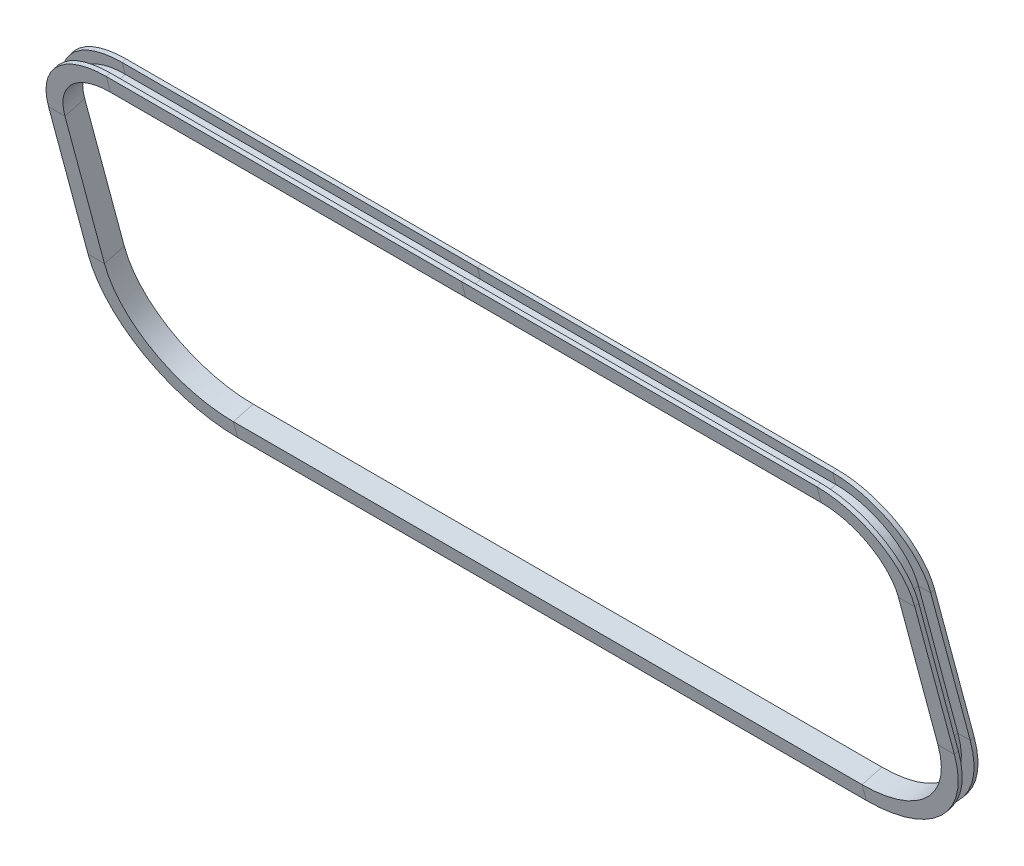
SolidWorks part; units mm, degrees
ref_plane "Front Plane" through (0, 0, 0) normal (0, 0, 1) x (1, 0, 0)
ref_plane "Top Plane" through (0, 0, 0) normal (0, 1, 0) x (1, 0, 0)
ref_plane "Right Plane" through (0, 0, 0) normal (1, 0, 0) x (0, 0, -1)
sketch3d "3DSketch1"
  line L0 (-101.75, 45, 0) -> (101.75, -45, 0) construction
  line L1 (-101.75, 45, 0) -> (101.75, 45, 0)
  line L2 (-101.75, 45, 0) -> (-101.75, -45, 0)
  line L3 (-101.75, -45, 0) -> (101.75, -45, 0)
  line L4 (101.75, 45, 0) -> (101.75, -45, 0)
  line L5 (-101.75, -45, 0) -> (-101.75, -45, -20)
  line L6 (-101.75, -45, -20) -> (-101.75, 45, -20)
  line L7 (-101.75, 45, -20) -> (-101.75, 45, 0)
  dimension "D1" = 203.5
  dimension "D2" = 90
  dimension "D3" = 20
sketch3d "3DSketch2"
  line L0 (-101.75, -45, -20) -> (-101.75, 29.641, 0)
  line L1 (-101.75, -45, 0) -> (-101.75, -45, -20) construction
  line L2 (-101.75, 45, 0) -> (-101.75, -45, 0) construction
  line L3 (-101.75, 29.641, 0) -> (101.75, 29.641, 0)
  line L4 (101.75, 45, 0) -> (101.75, -45, 0) construction
  line L5 (101.75, 29.641, 0) -> (101.75, -45, -20)
  line L6 (101.75, -45, -20) -> (-101.75, -45, -20)
  line L7 (-101.75, -45, -20) -> (-101.75, 45, -20) construction
  dimension "D1" = 15
sketch3d "3DSketch3"
  line L0 (-118.8022, 45, -32.4453) -> (-118.8022, -45, -32.4453) construction
  line L1 (-118.8022, -45, -32.4453) -> (-69.3047, -45, 17.0522) construction
  line L2 (-69.3047, -45, 17.0522) -> (-69.3047, 45, 17.0522) construction
  line L3 (-69.3047, 45, 17.0522) -> (-118.8022, 45, -32.4453)
  line L4 (-118.8022, 45, -32.4453) -> (-101.75, -45, -49.4975) construction
  line L5 (-118.8022, -45, -32.4453) -> (-69.3047, -45, -32.4453) construction
  line L6 (-101.75, -45, -49.4975) -> (-52.2525, -45, 0)
  line L7 (-52.2525, -45, 0) -> (-69.3047, 45, 17.0522)
  line L8 (-69.3047, -45, -32.4453) -> (-69.3047, -45, 17.0522) construction
  line L9 (-101.75, -45, -49.4975) -> (-118.8022, -45, -32.4453) construction
  line L10 (-94.0534, 45, -7.6966) -> (-94.0534, 45, 0) construction
  line L11 (-94.0534, 45, 0) -> (-101.75, 45, 0) construction
  line L12 (-77.0013, -45, -24.7487) -> (-101.75, -45, -24.7487) construction
  line L13 (-101.75, -45, -24.7487) -> (-101.75, -45, 0) construction
  line L14 (-52.2525, -45, 0) -> (-69.3047, -45, 0) construction
  line L15 (-69.3047, -45, 0) -> (-69.3047, -45, 17.0522) construction
  line L16 (-101.75, -45, 0) -> (101.75, -45, 0) construction
  line L17 (-101.75, -45, -49.4975) -> (-101.75, 45, -49.4975) construction
  line L18 (-101.75, 45, -49.4975) -> (-101.75, 45, -15.3931) construction
  line L19 (-101.75, -45, -49.4975) -> (-101.75, 45, -15.3931)
  line L20 (-82.0326, 45, 4.3243) -> (-61.9842, 6.363, 9.7317)
  point P0 (-94.0534, 45, -7.6966)
  point P11 (-77.0013, -45, -24.7487)
  dimension "D1" = 15
  dimension "D2" = 45
  dimension "D3" = 70
  dimension "D4" = 18
  dimension "D5" = 40
ref_plane "Plane4" through (0, 1.9856, -7.4103) normal (0, -0.2588, 0.9659) x (1, 0, 0)
ref_plane "Plane5" through (-32.3311, -12.2515, 32.3311) normal (0.683, 0.2588, -0.683) x (-0.7304, 0.242, -0.6387)
sketch "Sketch3" plane through (0, 1.9856, -7.4103) normal (0, -0.2588, 0.9659) x (1, 0, 0)
  line L0 (101.75, 28.631) -> (101.75, -48.643) construction
  line L1 (101.75, -48.643) -> (-101.75, -48.643) construction
  line L2 (-101.75, -48.643) -> (-101.75, 28.631) construction
  line L3 (-101.75, 28.631) -> (101.75, 28.631) construction
  line L4 (101.75, 13.631) -> (101.75, -23.643)
  line L5 (76.75, -48.643) -> (-76.75, -48.643)
  line L6 (-101.75, -23.643) -> (-101.75, 13.631)
  line L7 (-86.75, 28.631) -> (86.75, 28.631)
  arc A0 (-101.75, 13.631) -> (-86.75, 28.631) centre (-86.75, 13.631) cw
  arc A1 (101.75, 13.631) -> (86.75, 28.631) centre (86.75, 13.631) ccw
  arc A2 (101.75, -23.643) -> (76.75, -48.643) centre (76.75, -23.643) cw
  arc A3 (-76.75, -48.643) -> (-101.75, -23.643) centre (-76.75, -23.643) cw
  point P16 (-101.75, 8.8883)
  point P17 (-101.75, 9.2608)
  point P18 (-101.75, 9.674)
  point P19 (-101.75, 8.5099)
  point P20 (-101.75, 10.1009)
  point P21 (-101.75, 10.4954)
  point P22 (-101.75, 10.9218)
  point P23 (-101.75, 11.3232)
  point P24 (-101.75, 8.0855)
  point P25 (-101.75, 7.6175)
  point P26 (-101.75, 7.0517)
  point P27 (-101.75, 6.5911)
  point P28 (-101.75, 6.3551)
  point P29 (-101.75, 11.6823)
  point P30 (-101.75, 12.0079)
  point P31 (-101.75, 12.2696)
  point P32 (-101.75, 12.5331)
  point P33 (-101.75, 12.779)
  point P34 (-101.75, 13.0363)
  point P35 (-101.75, 13.3551)
  point P36 (-101.7349, 14.3045)
  point P37 (-101.7063, 14.7751)
  point P38 (-101.6613, 15.2595)
  point P39 (-101.6, 15.7469)
  point P40 (-101.5022, 16.3464)
  point P41 (-101.3854, 16.9181)
  point P42 (-101.2577, 17.4425)
  point P43 (-101.0481, 18.1658)
  point P44 (-100.8045, 18.8724)
  point P45 (-100.5182, 19.584)
  point P46 (-100.1658, 20.3405)
  point P47 (-99.7731, 21.0741)
  point P48 (-99.3112, 21.8296)
  point P49 (-98.8341, 22.5178)
  point P50 (-98.119, 23.416)
  point P51 (-97.4975, 24.0948)
  point P52 (-96.9583, 24.6215)
  point P53 (-96.3572, 25.1507)
  point P54 (-95.7062, 25.6637)
  point P55 (-95.0399, 26.1321)
  point P56 (-94.4307, 26.5154)
  point P57 (-93.518, 27.0173)
  point P58 (-92.413, 27.5209)
  point P59 (-91.7888, 27.7594)
  point P60 (-91.2239, 27.9483)
  point P61 (-90.7241, 28.095)
  point P62 (-90.2424, 28.2188)
  point P63 (-89.7763, 28.3226)
  point P64 (-89.2322, 28.4242)
  point P65 (-88.6806, 28.5063)
  point P66 (-88.1887, 28.5619)
  point P67 (-87.7468, 28.5979)
  point P68 (-87.2084, 28.624)
  point P69 (-86.664, 28.631)
  point P70 (-86.9729, 28.6294)
  point P71 (-86.5769, 28.631)
  point P72 (-86.4416, 28.631)
  point P73 (-87.4769, 28.6134)
  point P74 (-87.9918, 28.5795)
  point P75 (-88.4937, 28.5293)
  point P76 (-89.0402, 28.4552)
  point P77 (-88.8769, 28.4795)
  point P78 (-89.4185, 28.3917)
  point P79 (-90.0186, 28.2706)
  point P80 (-89.5918, 28.3594)
  point P81 (-90.4727, 28.1617)
  point P82 (-92.9852, 27.2737)
  point P83 (-91.9583, 27.6978)
  point P84 (-91.5185, 27.8529)
  point P85 (-92.2082, 27.6027)
  point P86 (-92.6943, 27.4029)
  point P87 (-86.092, 28.631)
  point P88 (-85.9372, 28.631)
  point P89 (-85.7467, 28.631)
  point P90 (-85.6091, 28.631)
  point P91 (-85.4413, 28.631)
  point P92 (-85.3162, 28.631)
  point P93 (-85.1205, 28.631)
  point P94 (-84.9101, 28.631)
  point P95 (-86.2993, 28.631)
  point P96 (-84.691, 28.631)
  point P97 (-84.5068, 28.631)
  point P98 (-84.3367, 28.631)
  point P99 (-84.2282, 28.631)
  point P100 (-84.1215, 28.631)
  point P101 (-84.0407, 28.631)
  point P102 (-83.9539, 28.631)
  point P103 (-83.8796, 28.631)
  point P104 (-83.8203, 28.631)
  point P105 (-83.7954, 28.631)
  point P106 (-83.7374, 28.631)
  point P107 (-83.6976, 28.631)
  point P108 (-83.7161, 28.631)
  point P109 (-83.6762, 28.631)
  point P110 (-83.6554, 28.631)
  point P111 (-83.6333, 28.631)
  point P112 (-83.6154, 28.631)
  point P113 (-83.5539, 28.631)
  point P114 (-83.5892, 28.631)
  point P115 (-83.5248, 28.631)
  point P116 (-83.4789, 28.631)
  point P117 (-83.4429, 28.631)
  point P118 (-83.4159, 28.631)
  point P119 (-83.3923, 28.631)
  point P120 (-83.3707, 28.631)
  point P121 (-83.3452, 28.631)
  point P122 (-83.3356, 28.631)
  point P123 (-83.3223, 28.631)
  point P124 (-83.3134, 28.631)
  point P125 (-83.3034, 28.631)
  point P126 (-83.2933, 28.631)
  point P127 (-83.2831, 28.631)
  point P128 (-83.2715, 28.631)
  point P129 (-83.261, 28.631)
  point P130 (-83.2485, 28.631)
  point P131 (-83.2402, 28.631)
  point P132 (-83.2319, 28.631)
  point P133 (-83.2237, 28.631)
  point P134 (-83.2152, 28.631)
  point P135 (-83.2069, 28.631)
  point P136 (-83.1959, 28.631)
  point P137 (-83.1812, 28.631)
  point P138 (-83.1782, 28.631)
  point P139 (-83.1745, 28.631)
  point P140 (-83.1692, 28.631)
  point P141 (-83.1633, 28.631)
  point P142 (-83.1343, 28.631)
  point P143 (-83.1229, 28.631)
  point P144 (-83.1168, 28.631)
  point P145 (-83.0272, 28.631)
  point P146 (-83.0238, 28.631)
  point P147 (-83.0188, 28.631)
  point P148 (-83.0138, 28.631)
  point P149 (-83.0347, 28.631)
  point P150 (-83.0096, 28.631)
  point P151 (-82.9931, 28.631)
  point P152 (-82.982, 28.631)
  point P153 (-82.941, 28.631)
  point P154 (-82.8091, 28.631)
  point P155 (-82.8277, 28.631)
  point P156 (-82.8585, 28.631)
  point P157 (-82.7985, 28.631)
  point P158 (-82.6875, 28.631)
  point P159 (-82.7105, 28.631)
  point P160 (-82.6678, 28.631)
  point P161 (-82.6454, 28.631)
  point P162 (-82.7646, 28.631)
  point P163 (-80.8571, 28.631)
  point P164 (-77.557, 28.631)
  point P165 (-74.2774, 28.631)
  point P166 (-71.8979, 28.631)
  point P167 (-65.9868, 28.631)
  point P168 (-60.1956, 28.631)
  point P169 (-54.1139, 28.631)
  point P170 (-51.7977, 28.631)
  point P171 (-48.316, 28.631)
  point P172 (-28.0351, 28.631)
  point P173 (-5.9621, 28.631)
  point P174 (-11.149, 28.631)
  point P175 (-2.6763, 28.631)
  point P176 (8.3817, 28.631)
  point P177 (19.8325, 28.631)
  point P178 (31.4841, 28.631)
  point P179 (55.9804, 28.631)
  point P180 (67.2703, 28.631)
  point P181 (77.3147, 28.631)
  point P182 (75.468, 28.631)
  point P183 (74.0138, 28.631)
  point P184 (72.3492, 28.631)
  point P185 (71.0011, 28.631)
  point P186 (78.8057, 28.631)
  point P187 (81.3017, 28.631)
  point P188 (82.4731, 28.631)
  point P189 (83.8516, 28.631)
  point P190 (84.5318, 28.631)
  point P191 (85.2739, 28.631)
  point P192 (86.3634, 28.631)
  point P193 (87.091, 28.6271)
  point P194 (87.512, 28.6117)
  point P195 (87.8301, 28.5921)
  point P196 (88.2171, 28.5591)
  point P197 (88.5489, 28.5228)
  point P198 (88.7932, 28.4912)
  point P199 (87.3076, 28.6207)
  point P200 (86.928, 28.63)
  point P201 (87.6792, 28.6022)
  point P202 (88.0093, 28.5781)
  point P203 (88.3935, 28.5407)
  point P204 (88.6806, 28.5063)
  point P205 (88.2956, 28.5512)
  point P206 (86.4887, 28.631)
  point P207 (86.2192, 28.631)
  point P208 (86.621, 28.631)
  point P209 (86.1013, 28.631)
  point P210 (89.0396, 28.4553)
  point P211 (88.9139, 28.4741)
  point P212 (89.1877, 28.4316)
  point P213 (89.3876, 28.3973)
  point P214 (89.5918, 28.3594)
  point P215 (89.7763, 28.3226)
  point P216 (89.9445, 28.2869)
  point P217 (90.126, 28.2462)
  point P218 (90.5566, 28.14)
  point P219 (90.3748, 28.1865)
  point P220 (90.7818, 28.079)
  point P221 (90.2412, 28.2191)
  point P222 (90.9304, 28.0367)
  point P223 (90.6654, 28.111)
  point P224 (91.0234, 28.0094)
  point P225 (91.1193, 27.9806)
  point P226 (91.0671, 27.9963)
  point P227 (91.1601, 27.9681)
  point P228 (91.2239, 27.9483)
  point P229 (91.2919, 27.9269)
  point P230 (91.3672, 27.9027)
  point P231 (91.4432, 27.8779)
  point P232 (91.5278, 27.8497)
  point P233 (91.4863, 27.8636)
  point P234 (91.4016, 27.8916)
  point P235 (91.3272, 27.9156)
  point P236 (90.853, 28.059)
  point P237 (90.7241, 28.095)
  point P238 (90.4597, 28.1651)
  point P239 (90.606, 28.1269)
  point P240 (90.295, 28.2061)
  point P241 (91.7546, 27.7715)
  point P242 (91.61, 27.8219)
  point P243 (91.6909, 27.7939)
  point P244 (91.8359, 27.7425)
  point P245 (91.9382, 27.7052)
  point P246 (92.0266, 27.6723)
  point P247 (92.5429, 27.4673)
  point P248 (92.3114, 27.562)
  point P249 (92.2207, 27.5978)
  point P250 (92.743, 27.3818)
  point P251 (92.9994, 27.2672)
  point P252 (92.6641, 27.4159)
  point P253 (93.139, 27.2024)
  point P254 (93.3347, 27.1085)
  point P255 (94.2347, 26.6302)
  point P256 (93.8576, 26.8402)
  point P257 (94.5098, 26.4679)
  point P258 (94.9189, 26.2115)
  point P259 (95.2541, 25.9874)
  point P260 (95.6705, 25.6902)
  point P261 (95.9778, 25.4567)
  point P262 (96.3572, 25.1507)
  point P263 (96.7839, 24.781)
  point P264 (97.0648, 24.5216)
  point P265 (97.122, 24.4671)
  point P266 (97.276, 24.3176)
  point P267 (97.343, 24.2512)
  point P268 (97.2008, 24.3912)
  point P269 (96.8935, 24.6813)
  point P270 (97.4975, 24.0948)
  point P271 (97.6271, 23.9601)
  point P272 (97.9319, 23.6293)
  point P273 (98.224, 23.2926)
  point P274 (98.4968, 22.9591)
  point P275 (99.9654, 20.7271)
  point P276 (100.2668, 20.1346)
  point P277 (100.5366, 19.5411)
  point P278 (99.3468, 21.7747)
  point P279 (99.7731, 21.0741)
  point P280 (98.9281, 22.3886)
  point P281 (100.9526, 18.4565)
  point P282 (101.4578, 16.5772)
  point P283 (101.2391, 17.5125)
  point P284 (101.0789, 18.0676)
  point P285 (101.7349, 14.3045)
  point P286 (101.75, 11.6823)
  point P287 (101.75, 12.5331)
  point P288 (101.75, 10.1009)
  point P289 (101.75, 8.7163)
  point P290 (101.75, 7.0517)
  point P291 (101.75, 5.873)
  point P292 (101.75, 4.8975)
  point P293 (101.75, 3.4586)
  point P294 (101.75, 1.9732)
  point P295 (101.75, 7.9192)
  point P296 (101.75, 9.674)
  point P297 (101.75, 10.9218)
  point P298 (101.75, -0.5378)
  point P299 (101.75, 0.2836)
  point P300 (101.75, 1.0975)
  point P301 (101.75, -1.2342)
  point P302 (101.75, -2.4229)
  point P303 (101.75, -3.3673)
  point P304 (101.75, -6.089)
  point P305 (101.75, -4.202)
  point P306 (101.75, -7.4897)
  point P307 (101.75, -8.9583)
  point P308 (101.75, -12.1668)
  point P309 (101.75, -15.5849)
  point P310 (101.75, -13.2269)
  point P311 (101.75, -16.7901)
  point P312 (101.75, -18.8758)
  point P313 (101.75, -20.6779)
  point P314 (101.75, -22.5371)
  point P315 (101.75, -11.606)
  point P316 (101.7104, -25.0494)
  point P317 (101.7401, -24.3463)
  point P318 (101.5937, -26.4339)
  point P319 (101.4342, -27.6038)
  point P320 (101.0091, -29.6844)
  point P321 (100.5366, -31.337)
  point P322 (99.9654, -32.9191)
  point P323 (99.3468, -34.3381)
  point P324 (98.4968, -35.975)
  point P325 (97.1872, -38.0417)
  point P326 (95.7612, -39.878)
  point P327 (92.9994, -42.6419)
  point P328 (90.9304, -44.2323)
  point P329 (88.3935, -45.7661)
  point P330 (86.1013, -46.8282)
  point P331 (84.2548, -47.49)
  point P332 (82.7408, -47.9146)
  point P333 (80.7574, -48.3198)
  point P334 (82.185, -48.0451)
  point P335 (79.6746, -48.4714)
  point P336 (77.9461, -48.6144)
  point P337 (77.3147, -48.6367)
  point P338 (78.8057, -48.5584)
  point P339 (81.3017, -48.2252)
  point P340 (83.4738, -47.7219)
  point P341 (85.2739, -47.145)
  point P342 (86.8459, -46.5138)
  point P343 (89.3876, -45.2136)
  point P344 (92.0266, -43.4326)
  point P345 (75.5633, -48.643)
  point P346 (74.0138, -48.643)
  point P347 (72.666, -48.643)
  point P348 (76.177, -48.643)
  point P349 (70.4954, -48.643)
  point P350 (68.2255, -48.643)
  point P351 (66.332, -48.643)
  point P352 (64.8169, -48.643)
  point P353 (62.3576, -48.643)
  point P354 (60.3082, -48.643)
  point P355 (58.4657, -48.643)
  point P356 (56.1337, -48.643)
  point P357 (53.7809, -48.643)
  point P358 (50.0366, -48.643)
  point P359 (46.8371, -48.643)
  point P360 (51.8818, -48.643)
  point P361 (43.8142, -48.643)
  point P362 (40.445, -48.643)
  point P363 (32.0733, -48.643)
  point P364 (35.4458, -48.643)
  point P365 (27.4568, -48.643)
  point P366 (21.6092, -48.643)
  point P367 (16.8249, -48.643)
  point P368 (13.5176, -48.643)
  point P369 (6.6543, -48.643)
  point P370 (9.5435, -48.643)
  point P371 (2.9698, -48.643)
  point P372 (-4.6265, -48.643)
  point P373 (-1.8105, -48.643)
  point P374 (-7.817, -48.643)
  point P375 (-15.2392, -48.643)
  point P376 (-22.4973, -48.643)
  point P377 (-37.4144, -48.643)
  point P378 (-40.9591, -48.643)
  point P379 (-29.5201, -48.643)
  point P380 (-47.5436, -48.643)
  point P381 (-53.8188, -48.643)
  point P382 (-62.2067, -48.643)
  point P383 (-69.9853, -48.643)
  point P384 (-65.2788, -48.643)
  point P385 (-73.3764, -48.643)
  point P386 (-58.9928, -48.643)
  point P387 (-76.258, -48.643)
  point P388 (-51.0057, -48.643)
  point P389 (-44.2037, -48.643)
  point P390 (-78.6769, -48.5687)
  point P391 (-80.0995, -48.4176)
  point P392 (-79.4248, -48.4995)
  point P393 (-80.9985, -48.2794)
  point P394 (-82.7105, -47.9221)
  point P395 (-84.7713, -47.3213)
  point P396 (-85.3162, -47.1296)
  point P397 (-86.514, -46.6575)
  point P398 (-83.8203, -47.6224)
  point P399 (-85.8409, -46.9316)
  point P400 (-87.0724, -46.4125)
  point P401 (-81.914, -48.1039)
  point P402 (-83.4429, -47.7305)
  point P403 (-84.2548, -47.49)
  point P404 (-88.1172, -45.9093)
  point P405 (-87.6853, -46.1246)
  point P406 (-88.5743, -45.67)
  point P407 (-89.099, -45.3802)
  point P408 (-89.4571, -45.1728)
  point P409 (-89.6971, -45.0293)
  point P410 (-90.0922, -44.7851)
  point P411 (-91.047, -44.1515)
  point P412 (-91.9583, -43.4851)
  point P413 (-96.0712, -39.5079)
  point P414 (-96.7105, -38.6955)
  point P415 (-97.965, -36.869)
  point P416 (-98.5659, -35.8523)
  point P417 (-98.9262, -35.1849)
  point P418 (-98.3057, -36.3061)
  point P419 (-97.3158, -37.8574)
  point P420 (-96.9583, -38.3612)
  point P421 (-97.111, -38.1493)
  point P422 (-96.8015, -38.5741)
  point P423 (-99.1995, -34.644)
  point P424 (-99.5618, -33.8715)
  point P425 (-100.1578, -32.4223)
  point P426 (-99.8647, -33.1672)
  point P427 (-100.7333, -30.7002)
  point P428 (-100.9145, -30.0523)
  point P429 (-100.5182, -31.3938)
  point P430 (-101.6922, -25.3428)
  point P431 (-101.4139, -27.7289)
  point P432 (-101.75, -17.0233)
  point P433 (-101.75, -13.3842)
  point P434 (-101.75, -18.7376)
  point P435 (-101.75, -22.213)
  point P436 (-101.75, -15.2049)
  point P437 (-101.75, -11.606)
  point P438 (-101.75, -7.2336)
  point P439 (-101.75, 4.3683)
  point P440 (-101.75, 1.7765)
  point P441 (-101.75, -1.6271)
  point P442 (-101.75, 5.1817)
  point P443 (-101.75, -2.845)
  point P444 (-95.5107, -40.1668)
  point P445 (-94.1583, -41.586)
  point P446 (-93.2565, -42.419)
  point P447 (-95.0149, -40.7133)
  point P448 (-92.5914, -42.9834)
  point P449 (-92.9852, -42.654)
  point P450 (-93.6251, -42.0884)
  point P451 (-94.713, -41.0307)
  point P452 (-95.7612, -39.878)
  point P453 (-96.4178, -39.076)
  point P454 (-97.7014, -37.2826)
  point P455 (-101.5856, -26.5058)
  point P456 (-101.1711, -28.9917)
  point P457 (-101.75, -20.8519)
  point P458 (-37.4144, 28.631)
  point P459 (-19.999, 28.631)
  point P460 (46.8371, 28.631)
  point P461 (40.445, 28.631)
  point P462 (-43.2464, 28.631)
  point P463 (-33.0444, 28.631)
  point P464 (-24.3425, 28.631)
  point P465 (-15.6046, 28.631)
  point P466 (24.1254, 28.631)
  point P467 (14.429, 28.631)
  point P468 (62.8064, 28.631)
  point P469 (36.7101, 28.631)
  point P470 (51.1173, 28.631)
  point P471 (-33.9857, -48.643)
  point P472 (-19.4422, -48.643)
  point P473 (-26.2425, -48.643)
  point P474 (-101.75, -4.7598)
  point P475 (-101.75, 0.2836)
  point P476 (69.2327, 28.631)
  point P477 (43.8142, 28.631)
  point P478 (-69.5706, 28.631)
  point P479 (-63.1527, 28.631)
  point P480 (-57.1207, 28.631)
  point P481 (-11.149, -48.643)
  point P482 (11.1298, 28.631)
  point P483 (4.0759, 28.631)
  point P484 (0, 0)
  point P485 (0, 0)
  dimension "D1" = 15
  dimension "D2" = 25
ref_plane "Plane6" through (0, 0, 0) normal (1, 0, 0) x (0, 0, -1)
sketch "Sketch6" plane through (0, 0, 0) normal (1, 0, 0) x (0, 0, -1)
  line L0 (-1.0353, 33.5047) -> (0, 29.641)
  line L5 (0, 29.641) -> (-4.8296, 28.3469)
  line L6 (-4.8296, 28.3469) -> (-5.8649, 32.2106)
  line L7 (-5.8649, 32.2106) -> (-4.899, 32.4694)
  line L8 (-4.899, 32.4694) -> (-4.1225, 29.5717)
  line L9 (-4.1225, 29.5717) -> (-1.2247, 30.3481)
  line L10 (-1.2247, 30.3481) -> (-2.0012, 33.2459)
  line L11 (-2.0012, 33.2459) -> (-1.0353, 33.5047)
  line L12 (20, -45) -> (0, 29.641) construction
  dimension "D1" = 1
  dimension "D2" = 3
  dimension "D3" = 3
  dimension "D4" = 1
sweep "Sweep3" add profiles "Sketch6" path "Sketch3"
ref_plane "Plane7" through (0, 0, 0) normal (-0.183, 0.9659, 0.183) x (0.9831, 0.1798, 0.0341)
sketch3d "3DSketch7"
  line L0 (-73.6848, 28.9121, 6.5758) -> (-64.9273, 12.0348, 8.9379) construction
  line L1 (-101.75, -15.6913, -38.3913) -> (-101.75, 22.0144, -24.1032) construction
  line L2 (-75.7965, -47.8612, -24.6282) -> (-83.8383, -45, -31.5858) construction
  line L3 (-71.8237, -48.8637, -21.0353) -> (-75.1557, -48.0532, -24.0601) construction
  line L4 (-66.5037, -50.1578, -16.2056) -> (-65.9203, -50.2997, -15.676) construction
  line L5 (-71.8237, -48.8637, -21.0353) -> (-66.5037, -50.1578, -16.2056) construction
  line L6 (-60.8681, -48.7184, -10.0246) -> (-57.6828, -45, -5.4303) construction
  line L7 (-54.9515, -30.755, 2.699) -> (-60.8058, 0.1433, 8.5532) construction
  line L8 (-73.6848, 28.9121, 6.5758) -> (-64.9273, 12.0348, 8.9379) construction
  line L9 (-101.75, -15.6913, -38.3913) -> (-101.75, 22.0144, -24.1032) construction
  line L10 (-75.7965, -47.8612, -24.6282) -> (-83.8383, -45, -31.5858) construction
  line L11 (-71.8237, -48.8637, -21.0353) -> (-75.1557, -48.0532, -24.0601) construction
  line L12 (-66.5037, -50.1578, -16.2056) -> (-65.9203, -50.2997, -15.676) construction
  line L13 (-71.8237, -48.8637, -21.0353) -> (-66.5037, -50.1578, -16.2056) construction
  line L14 (-60.8681, -48.7184, -10.0246) -> (-57.6828, -45, -5.4303) construction
  line L15 (-54.9515, -30.755, 2.699) -> (-60.8058, 0.1433, 8.5532) construction
  line L16 (-101.75, -20.8519, -13.5295) -> (-101.75, 15.1521, -3.8823) construction
  line L17 (76.75, -45, -20) -> (-76.75, -45, -20) construction
  line L18 (101.75, 15.1521, -3.8823) -> (101.75, -20.8519, -13.5295) construction
  line L19 (-86.75, 29.641, 0) -> (86.75, 29.641, 0) construction
  line L20 (-101.75, -20.8519, -13.5295) -> (-101.75, 15.1521, -3.8823) construction
  line L21 (76.75, -45, -20) -> (-76.75, -45, -20) construction
  line L22 (101.75, 15.1521, -3.8823) -> (101.75, -20.8519, -13.5295) construction
  line L23 (-86.75, 29.641, 0) -> (86.75, 29.641, 0) construction
  arc A0 (-64.9273, 12.0348, 8.9379) -> (-60.8058, 0.1433, 8.5532) centre (-82.019, 0.1433, -12.66) ccw construction
  arc A1 (-75.7613, 32.4769, 5.8502) -> (-73.6848, 28.9121, 6.5758) centre (-90.7765, 17.0207, -15.022) ccw construction
  arc A2 (-75.7613, 32.4769, 5.8502) -> (-97.6387, 37.0111, -14.3091) centre (-85.7714, 22.1728, -8.0646) ccw construction
  arc A3 (-101.75, 22.0144, -24.1032) -> (-97.6387, 37.0111, -14.3091) centre (-79.8378, 14.7536, -4.9424) ccw construction
  arc A4 (-83.8383, -45, -31.5858) -> (-101.75, -15.6913, -38.3913) centre (-83.4898, -21.7419, -22.4239) ccw construction
  arc A5 (-75.1557, -48.0532, -24.0601) -> (-75.7965, -47.8612, -24.6282) centre (-75.6571, -38.558, -20.9635) ccw construction
  arc A6 (-65.9203, -50.2997, -15.676) -> (-60.8681, -48.7184, -10.0246) centre (-66.4217, -40.8045, -12.5794) ccw construction
  arc A7 (-57.6828, -45, -5.4303) -> (-54.9515, -30.755, 2.699) centre (-67.6794, -30.755, -10.0289) ccw construction
  arc A8 (-64.9273, 12.0348, 8.9379) -> (-60.8058, 0.1433, 8.5532) centre (-82.019, 0.1433, -12.66) ccw construction
  arc A9 (-75.7613, 32.4769, 5.8502) -> (-73.6848, 28.9121, 6.5758) centre (-90.7765, 17.0207, -15.022) ccw construction
  arc A10 (-75.7613, 32.4769, 5.8502) -> (-97.6387, 37.0111, -14.3091) centre (-85.7714, 22.1728, -8.0646) ccw construction
  arc A11 (-101.75, 22.0144, -24.1032) -> (-97.6387, 37.0111, -14.3091) centre (-79.8378, 14.7536, -4.9424) ccw construction
  arc A12 (-83.8383, -45, -31.5858) -> (-101.75, -15.6913, -38.3913) centre (-83.4898, -21.7419, -22.4239) ccw construction
  arc A13 (-75.1557, -48.0532, -24.0601) -> (-75.7965, -47.8612, -24.6282) centre (-75.6571, -38.558, -20.9635) ccw construction
  arc A14 (-65.9203, -50.2997, -15.676) -> (-60.8681, -48.7184, -10.0246) centre (-66.4217, -40.8045, -12.5794) ccw construction
  arc A15 (-57.6828, -45, -5.4303) -> (-54.9515, -30.755, 2.699) centre (-67.6794, -30.755, -10.0289) ccw construction
  arc A16 (-101.75, 15.1521, -3.8823) -> (-86.75, 29.641, 0) centre (-86.75, 15.1521, -3.8823) ccw construction
  arc A17 (-76.75, -45, -20) -> (-101.75, -20.8519, -13.5295) centre (-76.75, -20.8519, -13.5295) ccw construction
  arc A18 (101.75, -20.8519, -13.5295) -> (76.75, -45, -20) centre (76.75, -20.8519, -13.5295) ccw construction
  arc A19 (101.75, 15.1521, -3.8823) -> (86.75, 29.641, 0) centre (86.75, 15.1521, -3.8823) ccw construction
  arc A20 (-101.75, 15.1521, -3.8823) -> (-86.75, 29.641, 0) centre (-86.75, 15.1521, -3.8823) ccw construction
  arc A21 (-76.75, -45, -20) -> (-101.75, -20.8519, -13.5295) centre (-76.75, -20.8519, -13.5295) ccw construction
  arc A22 (101.75, -20.8519, -13.5295) -> (76.75, -45, -20) centre (76.75, -20.8519, -13.5295) ccw construction
  arc A23 (101.75, 15.1521, -3.8823) -> (86.75, 29.641, 0) centre (86.75, 15.1521, -3.8823) ccw construction
  spline S0 degree 3 number of poles 181 (-60.0718, -47.7888, -8.876) -> (-60.0718, -47.7888, -8.876)
  spline S1 degree 3 number of poles 107 (-101.7066, 16.2534, -3.5872) -> (-101.7066, 16.2534, -3.5872)
  spline S2 degree 3 number of poles 181 (60.0718, -47.7888, -8.876) -> (60.0718, -47.7888, -8.876)
  point P3 (-61.5286, 7.9079, -33.1503)
  point P5 (-61.5286, 7.9079, -33.1503)
  point P8 (-70.2861, 24.7853, -35.5124)
  point P9 (-70.2861, 24.7853, -35.5124)
  point P11 (-99.4317, 16.9964, 5.5956)
  point P13 (-99.4317, 16.9964, 5.5956)
  point P16 (-59.3474, 22.5182, -25.4328)
  point P17 (-59.3474, 22.5182, -25.4328)
  point P19 (-66.4145, -15.2714, -39.4993)
  point P22 (-68.827, -35.9698, -27.7936)
  point P23 (-66.4145, -15.2714, -39.4993)
  point P25 (-73.2519, -43.3927, -5.7492)
  point P28 (-79.9737, -35.4137, 2.2653)
  point P29 (-68.827, -35.9698, -27.7936)
  point P31 (0, 0, 0)
  point P34 (0, 0, 0)
  point P39 (-73.2519, -43.3927, -5.7492)
  point P45 (-79.9737, -35.4137, 2.2653)
  point P46 (-86.75, 19.0344, -18.3712)
  point P48 (-86.75, 19.0344, -18.3712)
  point P51 (-76.75, -14.3814, -37.6777)
  point P52 (-76.75, -14.3814, -37.6777)
  point P54 (76.75, -14.3814, -37.6777)
  point P57 (86.75, 11.2698, 10.6066)
  point P58 (76.75, -14.3814, -37.6777)
  point P62 (60.0718, -47.7888, -8.876)
  point P64 (86.75, 11.2698, 10.6066)
ref_point "Point214"
ref_point "Point215"
ref_point "Point216"
ref_point "Point217"
ref_point "Point218"
ref_point "Point219"
ref_point "Point220"
ref_point "Point221"
ref_point "Point222"
ref_point "Point223"
ref_point "Point224"
ref_point "Point225"
ref_point "Point226"
ref_point "Point227"
ref_point "Point228"
ref_point "Point229"
ref_point "Point230"
ref_point "Point231"
ref_point "Point232"
ref_point "Point233"
ref_point "Point234"
ref_point "Point235"
ref_point "Point236"
ref_point "Point237"
ref_point "Point238"
ref_point "Point239"
ref_point "Point240"
ref_point "Point241"
ref_point "Point242"
ref_point "Point243"
ref_point "Point244"
ref_point "Point245"
ref_point "Point246"
ref_point "Point247"
ref_point "Point248"
ref_point "Point249"
ref_point "Point250"
ref_point "Point251"
ref_point "Point252"
ref_point "Point253"
ref_point "Point254"
ref_point "Point255"
ref_point "Point256"
ref_point "Point257"
ref_point "Point258"
ref_point "Point259"
ref_point "Point260"
ref_point "Point261"
ref_point "Point262"
ref_point "Point263"
ref_point "Point264"
ref_point "Point265"
ref_point "Point266"
ref_point "Point267"
ref_point "Point268"
ref_point "Point269"
ref_point "Point270"
ref_point "Point271"
ref_point "Point272"
ref_point "Point273"
ref_point "Point274"
ref_point "Point275"
ref_point "Point276"
ref_point "Point277"
ref_point "Point278"
ref_point "Point279"
ref_point "Point280"
ref_point "Point281"
ref_point "Point282"
ref_point "Point283"
ref_point "Point284"
ref_point "Point285"
ref_point "Point286"
ref_point "Point287"
ref_point "Point288"
ref_point "Point289"
ref_point "Point290"
ref_point "Point291"
ref_point "Point292"
ref_point "Point293"
ref_point "Point294"
ref_point "Point295"
ref_point "Point296"
ref_point "Point297"
ref_point "Point298"
ref_point "Point299"
ref_point "Point300"
ref_point "Point301"
ref_point "Point302"
ref_point "Point303"
ref_point "Point304"
ref_point "Point305"
ref_point "Point306"
ref_point "Point307"
ref_point "Point308"
ref_point "Point309"
ref_point "Point310"
ref_point "Point311"
ref_point "Point312"
ref_point "Point313"
ref_point "Point314"
ref_point "Point315"
ref_point "Point316"
ref_point "Point317"
ref_point "Point318"
ref_point "Point319"
ref_point "Point320"
ref_point "Point321"
ref_point "Point322"
ref_point "Point323"
ref_point "Point324"
ref_point "Point325"
ref_point "Point326"
ref_point "Point327"
ref_point "Point328"
ref_point "Point329"
ref_point "Point330"
ref_point "Point331"
ref_point "Point332"
ref_point "Point333"
ref_point "Point334"
ref_point "Point335"
ref_point "Point336"
ref_point "Point337"
ref_point "Point338"
ref_point "Point339"
ref_point "Point340"
ref_point "Point341"
ref_point "Point342"
ref_point "Point343"
ref_point "Point344"
ref_point "Point345"
ref_point "Point346"
ref_point "Point347"
ref_point "Point348"
ref_point "Point349"
ref_point "Point350"
ref_point "Point351"
ref_point "Point352"
ref_point "Point353"
ref_point "Point354"
ref_point "Point355"
ref_point "Point356"
ref_point "Point357"
ref_point "Point358"
ref_point "Point359"
ref_point "Point360"
ref_point "Point361"
ref_point "Point362"
ref_point "Point363"
ref_point "Point364"
ref_point "Point365"
ref_point "Point366"
ref_point "Point367"
ref_point "Point368"
ref_point "Point369"
ref_point "Point370"
ref_point "Point371"
ref_point "Point372"
ref_point "Point373"
ref_point "Point374"
ref_point "Point375"
ref_point "Point376"
ref_point "Point377"
ref_point "Point378"
ref_point "Point379"
ref_point "Point380"
ref_point "Point381"
ref_point "Point382"
ref_point "Point383"
ref_point "Point384"
ref_point "Point385"
ref_point "Point386"
ref_point "Point387"
ref_point "Point388"
ref_point "Point389"
ref_point "Point390"
ref_point "Point391"
ref_point "Point392"
ref_point "Point393"
ref_point "Point394"
ref_point "Point395"
ref_point "Point396"
ref_point "Point397"
ref_point "Point398"
ref_point "Point399"
ref_point "Point400"
ref_point "Point401"
ref_point "Point402"
ref_point "Point403"
ref_point "Point404"
ref_point "Point405"
ref_point "Point406"
ref_point "Point407"
ref_point "Point408"
ref_point "Point409"
ref_point "Point410"
ref_point "Point411"
ref_point "Point412"
ref_point "Point413"
ref_point "Point414"
ref_point "Point415"
ref_point "Point416"
ref_point "Point417"
ref_point "Point418"
ref_point "Point419"
ref_point "Point420"
ref_point "Point421"
ref_point "Point422"
ref_point "Point423"
ref_point "Point424"
ref_point "Point425"
ref_point "Point426"
ref_point "Point427"
ref_point "Point428"
ref_point "Point429"
ref_point "Point430"
ref_point "Point431"
ref_point "Point432"
ref_point "Point433"
ref_point "Point434"
ref_point "Point435"
ref_point "Point436"
ref_point "Point437"
ref_point "Point438"
ref_point "Point439"
ref_point "Point440"
ref_point "Point441"
ref_point "Point442"
ref_point "Point443"
ref_point "Point444"
ref_point "Point445"
ref_point "Point446"
ref_point "Point447"
ref_point "Point448"
ref_point "Point449"
ref_point "Point450"
ref_point "Point451"
ref_point "Point452"
ref_point "Point453"
ref_point "Point454"
ref_point "Point455"
ref_point "Point456"
ref_point "Point457"
ref_point "Point458"
ref_point "Point459"
ref_point "Point460"
ref_point "Point461"
ref_point "Point462"
ref_point "Point463"
ref_point "Point464"
ref_point "Point465"
ref_point "Point466"
ref_point "Point467"
ref_point "Point468"
ref_point "Point469"
ref_point "Point470"
ref_point "Point471"
ref_point "Point472"
ref_point "Point473"
ref_point "Point474"
ref_point "Point475"
ref_point "Point476"
ref_point "Point477"
ref_point "Point478"
ref_point "Point479"
ref_point "Point480"
ref_point "Point481"
ref_point "Point482"
ref_point "Point483"
ref_point "Point484"
ref_point "Point485"
ref_point "Point486"
ref_point "Point487"
ref_point "Point488"
ref_point "Point489"
ref_point "Point490"
ref_point "Point491"
ref_point "Point492"
ref_point "Point493"
ref_point "Point494"
ref_point "Point495"
ref_point "Point496"
ref_point "Point497"
ref_point "Point498"
ref_point "Point499"
ref_point "Point500"
ref_point "Point501"
ref_point "Point502"
ref_point "Point503"
ref_point "Point504"
ref_point "Point505"
ref_point "Point506"
ref_point "Point507"
ref_point "Point508"
ref_point "Point509"
ref_point "Point510"
ref_point "Point511"
ref_point "Point512"
ref_point "Point513"
sketch3d "3DSketch8"
  point P0 (-60.0718, -47.7888, -8.876)
  point P2 (-61.3049, -49.1834, -10.6376)
  point P4 (-62.7988, -50.1247, -12.4883)
  point P6 (-64.5257, -50.4633, -14.3434)
  point P8 (-66.3758, -50.1889, -16.0895)
  point P10 (-68.2441, -49.7344, -17.7856)
  point P12 (-70.1124, -49.28, -19.4817)
  point P14 (-71.9807, -48.8255, -21.1778)
  point P16 (-73.8491, -48.371, -22.8739)
  point P18 (-75.7183, -47.8886, -24.5604)
  point P20 (-77.5907, -47.2228, -26.1805)
  point P22 (-79.4631, -46.5567, -27.8005)
  point P24 (-81.3355, -45.8905, -29.4204)
  point P26 (-83.2082, -45.2242, -31.0407)
  point P28 (-85.0785, -44.5074, -32.6393)
  point P30 (-86.9324, -43.5598, -34.1342)
  point P32 (-88.7502, -42.3856, -35.507)
  point P34 (-90.5127, -40.9945, -36.7424)
  point P36 (-92.2015, -39.401, -37.8273)
  point P38 (-93.7987, -37.6219, -38.7504)
  point P40 (-95.2876, -35.676, -39.5018)
  point P42 (-96.6525, -33.5836, -40.0739)
  point P44 (-97.8791, -31.3667, -40.4604)
  point P46 (-98.9544, -29.0488, -40.6574)
  point P48 (-99.8672, -26.654, -40.6627)
  point P50 (-100.6079, -24.2076, -40.4764)
  point P52 (-101.1687, -21.7355, -40.1004)
  point P54 (-101.5438, -19.2632, -39.5386)
  point P56 (-101.7291, -16.8169, -38.7969)
  point P58 (-101.75, -14.4128, -37.9068)
  point P60 (-101.75, -12.0152, -36.9983)
  point P62 (-101.75, -9.6176, -36.0898)
  point P64 (-101.75, -7.22, -35.1812)
  point P66 (-101.75, -4.8224, -34.2727)
  point P68 (-101.75, -2.4248, -33.3641)
  point P70 (-101.75, -0.0272, -32.4556)
  point P72 (-101.75, 2.3704, -31.547)
  point P74 (-101.75, 4.7681, -30.6385)
  point P76 (-101.75, 7.1657, -29.73)
  point P78 (-101.75, 9.5633, -28.8214)
  point P80 (-101.75, 11.9609, -27.9129)
  point P82 (-101.75, 14.3585, -27.0043)
  point P84 (-101.75, 16.7561, -26.0958)
  point P86 (-101.75, 19.1537, -25.1872)
  point P88 (-101.75, 21.5513, -24.2787)
  point P90 (-101.6985, 23.93, -23.3258)
  point P92 (-101.4893, 26.2427, -22.2402)
  point P94 (-101.1226, 28.4716, -21.0289)
  point P96 (-100.6005, 30.6004, -19.7001)
  point P98 (-99.9268, 32.6135, -18.2636)
  point P100 (-99.1065, 34.4962, -16.7299)
  point P102 (-98.1444, 36.2367, -15.1083)
  point P104 (-97.039, 37.8051, -13.4086)
  point P106 (-95.7614, 39.1283, -11.6296)
  point P108 (-94.317, 40.1727, -9.7893)
  point P110 (-92.7321, 40.9219, -7.9205)
  point P112 (-91.033, 41.3632, -6.0542)
  point P114 (-89.2476, 41.4897, -4.2209)
  point P116 (-87.405, 41.299, -2.4506)
  point P118 (-85.5357, 40.7945, -0.7724)
  point P120 (-83.6703, 39.9844, 0.786)
  point P122 (-81.8393, 38.8818, 2.1992)
  point P124 (-80.0729, 37.5051, 3.4439)
  point P126 (-78.4, 35.8768, 4.4997)
  point P128 (-76.8481, 34.0235, 5.3494)
  point P130 (-75.4413, 31.9776, 5.9809)
  point P132 (-74.1611, 29.8042, 6.4375)
  point P134 (-72.9793, 27.5526, 6.7661)
  point P136 (-71.8074, 25.2941, 7.0822)
  point P138 (-70.6355, 23.0357, 7.3983)
  point P140 (-69.4636, 20.7772, 7.7143)
  point P142 (-68.2917, 18.5187, 8.0304)
  point P144 (-67.1198, 16.2602, 8.3465)
  point P146 (-65.9479, 14.0018, 8.6626)
  point P148 (-64.7762, 11.7431, 8.9784)
  point P150 (-63.6858, 9.4338, 9.1937)
  point P152 (-62.7284, 7.0574, 9.2506)
  point P154 (-61.9117, 4.63, 9.1475)
  point P156 (-61.2401, 2.1695, 8.8867)
  point P158 (-60.7209, -0.3048, 8.4683)
  point P160 (-60.2515, -2.7819, 7.999)
  point P162 (-59.7823, -5.2585, 7.5298)
  point P164 (-59.3131, -7.7351, 7.0605)
  point P166 (-58.8438, -10.2117, 6.5913)
  point P168 (-58.3746, -12.6883, 6.1221)
  point P170 (-57.9053, -15.1649, 5.6528)
  point P172 (-57.4361, -17.6415, 5.1836)
  point P174 (-56.9669, -20.1181, 4.7143)
  point P176 (-56.4976, -22.5947, 4.2451)
  point P178 (-56.0284, -25.0714, 3.7759)
  point P180 (-55.5591, -27.548, 3.3066)
  point P182 (-55.0899, -30.0246, 2.8374)
  point P184 (-54.6854, -32.498, 2.3046)
  point P186 (-54.5328, -34.9362, 1.5332)
  point P188 (-54.6466, -37.2896, 0.5277)
  point P190 (-55.0243, -39.5107, -0.6917)
  point P192 (-55.6584, -41.5546, -2.1003)
  point P194 (-56.5359, -43.3795, -3.6693)
  point P196 (-57.6389, -44.9487, -5.367)
  point P198 (-58.8554, -46.3688, -7.1216)
  point P200 (60.0718, -47.7888, -8.876)
  point P202 (61.3049, -49.1834, -10.6376)
  point P204 (62.7988, -50.1247, -12.4883)
  point P206 (64.5257, -50.4633, -14.3434)
  point P208 (66.3758, -50.1889, -16.0895)
  point P210 (68.2441, -49.7344, -17.7856)
  point P212 (70.1124, -49.28, -19.4817)
  point P214 (71.9807, -48.8255, -21.1778)
  point P216 (73.8491, -48.371, -22.8739)
  point P218 (75.7183, -47.8886, -24.5604)
  point P220 (77.5907, -47.2228, -26.1805)
  point P222 (79.4631, -46.5567, -27.8005)
  point P224 (81.3355, -45.8905, -29.4204)
  point P226 (83.2082, -45.2242, -31.0407)
  point P228 (85.0785, -44.5074, -32.6393)
  point P230 (86.9324, -43.5598, -34.1342)
  point P232 (88.7502, -42.3856, -35.507)
  point P234 (90.5127, -40.9945, -36.7424)
  point P236 (92.2015, -39.401, -37.8273)
  point P238 (93.7987, -37.6219, -38.7504)
  point P240 (95.2876, -35.676, -39.5018)
  point P242 (96.6525, -33.5836, -40.0739)
  point P244 (97.8791, -31.3667, -40.4604)
  point P246 (98.9544, -29.0488, -40.6574)
  point P248 (99.8672, -26.654, -40.6627)
  point P250 (100.6079, -24.2076, -40.4764)
  point P252 (101.1687, -21.7355, -40.1004)
  point P254 (101.5438, -19.2632, -39.5386)
  point P256 (101.7291, -16.8169, -38.7969)
  point P258 (101.75, -14.4128, -37.9068)
  point P260 (101.75, -12.0152, -36.9983)
  point P262 (101.75, -9.6176, -36.0898)
  point P264 (101.75, -7.22, -35.1812)
  point P266 (101.75, -4.8224, -34.2727)
  point P268 (101.75, -2.4248, -33.3641)
  point P270 (101.75, -0.0272, -32.4556)
  point P272 (101.75, 2.3704, -31.547)
  point P274 (101.75, 4.7681, -30.6385)
  point P276 (101.75, 7.1657, -29.73)
  point P278 (101.75, 9.5633, -28.8214)
  point P280 (101.75, 11.9609, -27.9129)
  point P282 (101.75, 14.3585, -27.0043)
  point P284 (101.75, 16.7561, -26.0958)
  point P286 (101.75, 19.1537, -25.1872)
  point P288 (101.75, 21.5513, -24.2787)
  point P290 (101.6985, 23.93, -23.3258)
  point P292 (101.4893, 26.2427, -22.2402)
  point P294 (101.1226, 28.4716, -21.0289)
  point P296 (100.6005, 30.6004, -19.7001)
  point P298 (99.9268, 32.6135, -18.2636)
  point P300 (99.1065, 34.4962, -16.7299)
  point P302 (98.1444, 36.2367, -15.1083)
  point P304 (97.039, 37.8051, -13.4086)
  point P306 (95.7614, 39.1283, -11.6296)
  point P308 (94.317, 40.1727, -9.7893)
  point P310 (92.7321, 40.9219, -7.9205)
  point P312 (91.033, 41.3632, -6.0542)
  point P314 (89.2476, 41.4897, -4.2209)
  point P316 (87.405, 41.299, -2.4506)
  point P318 (85.5357, 40.7945, -0.7724)
  point P320 (83.6703, 39.9844, 0.786)
  point P322 (81.8393, 38.8818, 2.1992)
  point P324 (80.0729, 37.5051, 3.4439)
  point P326 (78.4, 35.8768, 4.4997)
  point P328 (76.8481, 34.0235, 5.3494)
  point P330 (75.4413, 31.9776, 5.9809)
  point P332 (74.1611, 29.8042, 6.4375)
  point P334 (72.9793, 27.5526, 6.7661)
  point P336 (71.8074, 25.2941, 7.0822)
  point P338 (70.6355, 23.0357, 7.3983)
  point P340 (69.4636, 20.7772, 7.7143)
  point P342 (68.2917, 18.5187, 8.0304)
  point P344 (67.1198, 16.2602, 8.3465)
  point P346 (65.9479, 14.0018, 8.6626)
  point P348 (64.7762, 11.7431, 8.9784)
  point P350 (63.6858, 9.4338, 9.1937)
  point P352 (62.7284, 7.0574, 9.2506)
  point P354 (61.9117, 4.63, 9.1475)
  point P356 (61.2401, 2.1695, 8.8867)
  point P358 (60.7209, -0.3048, 8.4683)
  point P360 (60.2515, -2.7819, 7.999)
  point P362 (59.7823, -5.2585, 7.5298)
  point P364 (59.3131, -7.7351, 7.0605)
  point P366 (58.8438, -10.2117, 6.5913)
  point P368 (58.3746, -12.6883, 6.1221)
  point P370 (57.9053, -15.1649, 5.6528)
  point P372 (57.4361, -17.6415, 5.1836)
  point P374 (56.9669, -20.1181, 4.7143)
  point P376 (56.4976, -22.5947, 4.2451)
  point P378 (56.0284, -25.0714, 3.7759)
  point P380 (55.5591, -27.548, 3.3066)
  point P382 (55.0899, -30.0246, 2.8374)
  point P384 (54.6854, -32.498, 2.3046)
  point P386 (54.5328, -34.9362, 1.5332)
  point P388 (54.6466, -37.2896, 0.5277)
  point P390 (55.0243, -39.5107, -0.6917)
  point P392 (55.6584, -41.5546, -2.1003)
  point P394 (56.5359, -43.3795, -3.6693)
  point P396 (57.6389, -44.9487, -5.367)
  point P398 (58.8554, -46.3688, -7.1216)
  point P400 (-101.7066, 16.2534, -3.5872)
  point P402 (-101.75, 11.162, -4.9514)
  point P404 (-101.75, 6.0696, -6.316)
  point P406 (-101.75, 0.9771, -7.6805)
  point P408 (-101.75, -4.1154, -9.045)
  point P410 (-101.75, -9.2079, -10.4095)
  point P412 (-101.75, -14.3004, -11.7741)
  point P414 (-101.75, -19.3928, -13.1386)
  point P416 (-101.4675, -24.4716, -14.4994)
  point P418 (-100.1355, -29.3891, -15.8171)
  point P420 (-97.7673, -33.9283, -17.0334)
  point P422 (-94.4679, -37.8882, -18.0944)
  point P424 (-90.3834, -41.0932, -18.9532)
  point P426 (-85.6949, -43.4014, -19.5716)
  point P428 (-80.6101, -44.7104, -19.9224)
  point P430 (-75.3535, -45, -20)
  point P432 (-70.0813, -45, -20)
  point P434 (-64.8092, -45, -20)
  point P436 (-59.5371, -45, -20)
  point P438 (-54.265, -45, -20)
  point P440 (-48.9929, -45, -20)
  point P442 (-43.7207, -45, -20)
  point P444 (-38.4486, -45, -20)
  point P446 (-33.1765, -45, -20)
  point P448 (-27.9044, -45, -20)
  point P450 (-22.6322, -45, -20)
  point P452 (-17.3601, -45, -20)
  point P454 (-12.088, -45, -20)
  point P456 (-6.8159, -45, -20)
  point P458 (-1.5438, -45, -20)
  point P460 (3.7284, -45, -20)
  point P462 (9.0005, -45, -20)
  point P464 (14.2726, -45, -20)
  point P466 (19.5447, -45, -20)
  point P468 (24.8169, -45, -20)
  point P470 (30.089, -45, -20)
  point P472 (35.3611, -45, -20)
  point P474 (40.6332, -45, -20)
  point P476 (45.9053, -45, -20)
  point P478 (51.1775, -45, -20)
  point P480 (56.4496, -45, -20)
  point P482 (61.7217, -45, -20)
  point P484 (66.9938, -45, -20)
  point P486 (72.266, -45, -20)
  point P488 (77.5383, -44.9882, -19.9968)
  point P490 (82.751, -44.294, -19.8108)
  point P492 (87.6982, -42.5613, -19.3466)
  point P494 (92.1603, -39.8667, -18.6245)
  point P496 (95.9396, -36.3296, -17.6768)
  point P498 (98.8686, -32.1067, -16.5453)
  point P500 (100.8176, -27.3851, -15.2801)
  point P502 (101.7002, -22.3747, -13.9376)
  point P504 (101.75, -17.2827, -12.5732)
  point P506 (101.75, -12.1902, -11.2086)
  point P508 (101.75, -7.0977, -9.8441)
  point P510 (101.75, -2.0052, -8.4796)
  point P512 (101.75, 3.0872, -7.1151)
  point P514 (101.75, 8.1797, -5.7505)
  point P516 (101.75, 13.2722, -4.386)
  point P518 (101.3828, 18.3383, -3.0285)
  point P520 (99.3527, 23.0096, -1.7769)
  point P522 (95.7815, 26.7204, -0.7826)
  point P524 (91.1059, 29.0167, -0.1673)
  point P526 (85.8989, 29.641, 0)
  point P528 (80.6256, 29.641, 0)
  point P530 (75.3535, 29.641, 0)
  point P532 (70.0814, 29.641, 0)
  point P534 (64.8093, 29.641, 0)
  point P536 (59.5371, 29.641, 0)
  point P538 (54.265, 29.641, 0)
  point P540 (48.9929, 29.641, 0)
  point P542 (43.7208, 29.641, 0)
  point P544 (38.4486, 29.641, 0)
  point P546 (33.1765, 29.641, 0)
  point P548 (27.9044, 29.641, 0)
  point P550 (22.6323, 29.641, 0)
  point P552 (17.3602, 29.641, 0)
  point P554 (12.088, 29.641, 0)
  point P556 (6.8159, 29.641, 0)
  point P558 (1.5438, 29.641, 0)
  point P560 (-3.7283, 29.641, 0)
  point P562 (-9.0005, 29.641, 0)
  point P564 (-14.2726, 29.641, 0)
  point P566 (-19.5447, 29.641, 0)
  point P568 (-24.8168, 29.641, 0)
  point P570 (-30.0889, 29.641, 0)
  point P572 (-35.3611, 29.641, 0)
  point P574 (-40.6332, 29.641, 0)
  point P576 (-45.9053, 29.641, 0)
  point P578 (-51.1774, 29.641, 0)
  point P580 (-56.4496, 29.641, 0)
  point P582 (-61.7217, 29.641, 0)
  point P584 (-66.9938, 29.641, 0)
  point P586 (-72.2659, 29.641, 0)
  point P588 (-77.538, 29.641, 0)
  point P590 (-82.8102, 29.641, 0)
  point P592 (-88.0808, 29.5839, -0.0153)
  point P594 (-93.143, 28.2592, -0.3703)
  point P596 (-97.4241, 25.3317, -1.1547)
  point P598 (-100.3997, 21.1601, -2.2725)
